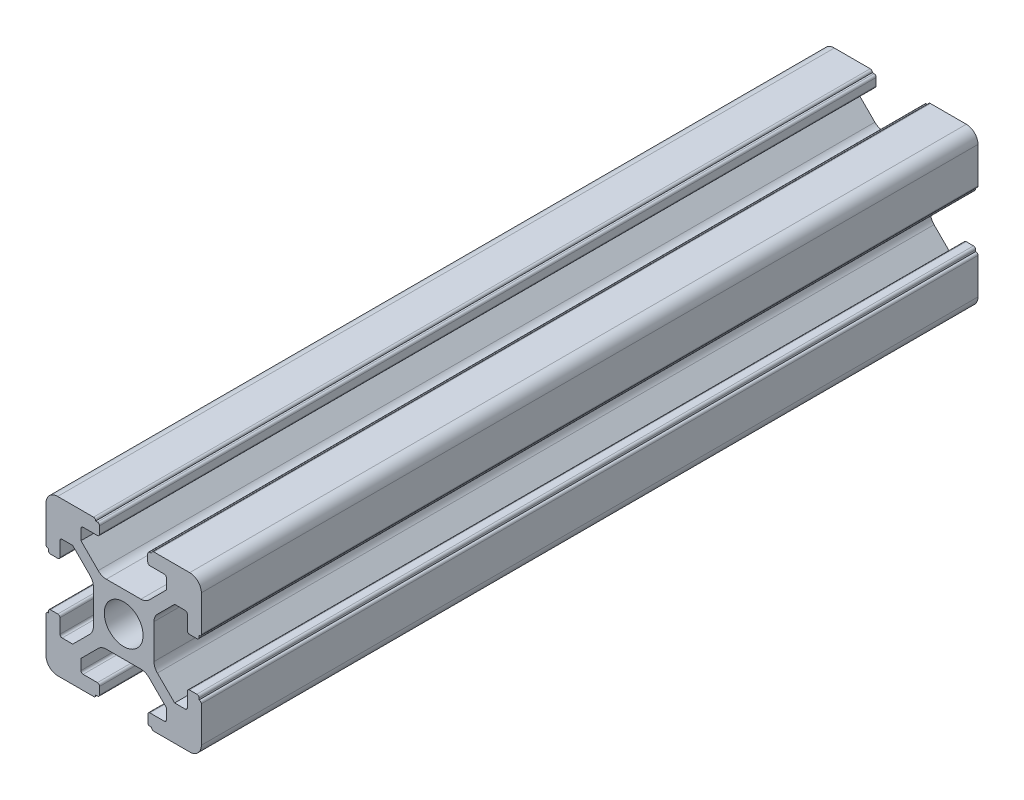
SolidWorks part; units mm, degrees
material "1060 Alloy"
ref_plane "Front Plane" through (0, 0, 0) normal (0, 0, 1) x (1, 0, 0)
ref_plane "Top Plane" through (0, 0, 0) normal (0, 1, 0) x (1, 0, 0)
ref_plane "Right Plane" through (0, 0, 0) normal (1, 0, 0) x (0, 0, -1)
sketch "Sketch1" plane through (0, 0, 0) normal (0, 0, 1) x (1, 0, 0)
  line L0 (3.8995, 3.9005) -> (10.4604, 10.4604) construction
  line L2 (-3.9002, 2.2177) -> (-3.9002, -2.2208)
  line L5 (-3.9005, 3.899) -> (3.9001, -3.8986) construction
  line L6 (-3.9, -3.901) -> (3.8995, 3.9005) construction
  line L7 (-0.0002, 10) -> (-0.0002, -9.9996) construction
  line L8 (-0.0002, -9.9996) -> (-0.0002, 10) construction
  line L9 (5.5006, 6.5619) -> (3.2793, 4.3405)
  line L14 (-10.0002, 9.9996) -> (9.9994, -10) construction
  line L15 (-9.9999, -10.0001) -> (9.9998, 10) construction
  line L16 (6.5613, 5.5012) -> (4.3401, 3.28)
  line L17 (-5.5002, 6.5603) -> (-3.279, 4.3391)
  line L18 (-6.5609, 5.4996) -> (-4.3395, 3.2783)
  line L19 (7.9206, 5.5012) -> (6.5613, 5.5012)
  line L20 (8.2006, 3.3812) -> (8.2006, 5.2212)
  line L21 (9.4206, 3.1012) -> (8.4806, 3.1012)
  line L22 (9.7006, 3.6012) -> (9.7006, 3.3812)
  line L23 (-8.5002, 9.9996) -> (-3.8802, 9.9996)
  line L24 (-3.6002, 9.7196) -> (-3.6002, 9.6996)
  line L25 (-3.6002, 9.6996) -> (-3.3802, 9.6996)
  line L26 (-3.1002, 9.4196) -> (-3.1002, 8.4796)
  line L27 (-3.3802, 8.1996) -> (-5.2202, 8.1996)
  line L28 (-5.5002, 7.9196) -> (-5.5002, 6.5603)
  line L29 (-7.9202, 5.4996) -> (-6.5609, 5.4996)
  line L30 (-8.2002, 3.3796) -> (-8.2002, 5.2196)
  line L31 (-9.4202, 3.0996) -> (-8.4802, 3.0996)
  line L32 (-9.7202, 3.5996) -> (-9.7002, 3.5996)
  line L33 (-9.7002, 3.5996) -> (-9.7002, 3.3796)
  line L34 (-10.0002, 8.4996) -> (-10.0002, 3.8796)
  line L35 (10.0006, 8.5012) -> (10.0006, 3.8812)
  line L36 (8.5006, 10.0012) -> (3.8806, 10.0012)
  line L37 (3.6006, 9.7012) -> (3.3806, 9.7012)
  line L38 (3.1006, 9.4212) -> (3.1006, 8.4812)
  line L39 (3.3806, 8.2012) -> (5.2206, 8.2012)
  line L40 (5.5006, 7.9212) -> (5.5006, 6.5619)
  line L41 (6.5629, -5.4996) -> (4.3415, -3.2783)
  line L42 (5.5022, -6.5603) -> (3.281, -4.3391)
  line L43 (5.5022, -7.9196) -> (5.5022, -6.5603)
  line L44 (3.3822, -8.1996) -> (5.2222, -8.1996)
  line L45 (3.1022, -9.4196) -> (3.1022, -8.4796)
  line L46 (3.6022, -9.6996) -> (3.3822, -9.6996)
  line L47 (8.5022, -9.9996) -> (3.8822, -9.9996)
  line L48 (10.0022, -8.4996) -> (10.0022, -3.8796)
  line L49 (9.7022, -3.5996) -> (9.7022, -3.3796)
  line L50 (9.4222, -3.0996) -> (8.4822, -3.0996)
  line L51 (8.2022, -3.3796) -> (8.2022, -5.2196)
  line L52 (7.9222, -5.4996) -> (6.5629, -5.4996)
  line L53 (-5.4986, -6.5619) -> (-3.2773, -4.3405)
  line L54 (-6.5593, -5.5012) -> (-4.3395, -3.2814)
  line L55 (-7.9186, -5.5012) -> (-6.5593, -5.5012)
  line L56 (-8.1986, -3.3812) -> (-8.1986, -5.2212)
  line L57 (-9.4186, -3.1012) -> (-8.4786, -3.1012)
  line L58 (-9.6986, -3.6012) -> (-9.6986, -3.3812)
  line L59 (-9.9986, -8.5012) -> (-9.9986, -3.8812)
  line L60 (-8.4986, -10.0012) -> (-3.8786, -10.0012)
  line L61 (-3.5986, -9.7012) -> (-3.3786, -9.7012)
  line L62 (-3.0986, -9.4212) -> (-3.0986, -8.4812)
  line L63 (-3.3786, -8.2012) -> (-5.2186, -8.2012)
  line L64 (-5.4986, -7.9212) -> (-5.4986, -6.5619)
  line L65 (-2.233, 3.8998) -> (2.2187, 3.9012)
  line L66 (3.9008, 2.234) -> (3.9022, -2.2177)
  line L67 (2.235, -3.8998) -> (-2.2167, -3.9012)
  line L68 (3.6006, 9.7212) -> (3.6006, 9.6996)
  line L69 (9.7006, 3.6012) -> (9.7206, 3.6012)
  line L70 (-9.6986, -3.6012) -> (-9.7186, -3.6012)
  line L71 (-3.5986, -9.7012) -> (-3.5986, -9.7212)
  line L72 (3.6022, -9.6996) -> (3.6022, -9.7196)
  line L73 (9.7222, -3.5996) -> (9.7022, -3.5996)
  arc A0 (-3.6002, 9.7196) -> (-3.8802, 9.9996) centre (-3.8802, 9.7196) ccw
  arc A1 (-3.3802, 9.6996) -> (-3.1002, 9.4196) centre (-3.3802, 9.4196) cw
  arc A2 (-3.1002, 8.4796) -> (-3.3802, 8.1996) centre (-3.3802, 8.4796) cw
  arc A3 (-10.0002, 8.4996) -> (-8.5002, 9.9996) centre (-8.5002, 8.4996) cw
  arc A4 (-8.2002, 3.3796) -> (-8.4802, 3.0996) centre (-8.4802, 3.3796) cw
  arc A5 (-9.4202, 3.0996) -> (-9.7002, 3.3796) centre (-9.4202, 3.3796) cw
  arc A6 (-9.7202, 3.5996) -> (-10.0002, 3.8796) centre (-9.7202, 3.8796) cw
  arc A7 (-3.279, 4.3391) -> (-2.233, 3.8998) centre (-2.2183, 5.3997) ccw
  arc A8 (-4.3395, 3.2783) -> (-3.9002, 2.2177) centre (-5.4002, 2.2177) cw
  arc A9 (-7.9202, 5.4996) -> (-8.2002, 5.2196) centre (-7.9202, 5.2196) ccw
  arc A10 (-5.2202, 8.1996) -> (-5.5002, 7.9196) centre (-5.2202, 7.9196) ccw
  arc A12 (-4.3395, -3.2814) -> (-3.9002, -2.2208) centre (-5.4002, -2.2208) ccw
  arc A13 (8.2006, 5.2212) -> (7.9206, 5.5012) centre (7.9206, 5.2212) ccw
  arc A14 (8.4806, 3.1012) -> (8.2006, 3.3812) centre (8.4806, 3.3812) cw
  arc A15 (9.7006, 3.3812) -> (9.4206, 3.1012) centre (9.4206, 3.3812) cw
  arc A16 (9.7206, 3.6012) -> (10.0006, 3.8812) centre (9.7206, 3.8812) ccw
  arc A17 (8.5006, 10.0012) -> (10.0006, 8.5012) centre (8.5006, 8.5012) cw
  arc A18 (3.6006, 9.7212) -> (3.8806, 10.0012) centre (3.8806, 9.7212) cw
  arc A19 (3.1006, 9.4212) -> (3.3806, 9.7012) centre (3.3806, 9.4212) cw
  arc A20 (3.3806, 8.2012) -> (3.1006, 8.4812) centre (3.3806, 8.4812) cw
  arc A21 (5.5006, 7.9212) -> (5.2206, 8.2012) centre (5.2206, 7.9212) ccw
  arc A22 (3.2793, 4.3405) -> (2.2187, 3.9012) centre (2.2187, 5.4012) cw
  arc A23 (4.3401, 3.28) -> (3.9008, 2.234) centre (5.4007, 2.2193) ccw
  arc A25 (5.2222, -8.1996) -> (5.5022, -7.9196) centre (5.2222, -7.9196) ccw
  arc A26 (3.1022, -8.4796) -> (3.3822, -8.1996) centre (3.3822, -8.4796) cw
  arc A27 (3.3822, -9.6996) -> (3.1022, -9.4196) centre (3.3822, -9.4196) cw
  arc A28 (3.6022, -9.7196) -> (3.8822, -9.9996) centre (3.8822, -9.7196) ccw
  arc A29 (10.0022, -8.4996) -> (8.5022, -9.9996) centre (8.5022, -8.4996) cw
  arc A30 (9.7222, -3.5996) -> (10.0022, -3.8796) centre (9.7222, -3.8796) cw
  arc A31 (9.4222, -3.0996) -> (9.7022, -3.3796) centre (9.4222, -3.3796) cw
  arc A32 (8.2022, -3.3796) -> (8.4822, -3.0996) centre (8.4822, -3.3796) cw
  arc A33 (7.9222, -5.4996) -> (8.2022, -5.2196) centre (7.9222, -5.2196) ccw
  arc A34 (4.3415, -3.2783) -> (3.9022, -2.2177) centre (5.4022, -2.2177) cw
  arc A35 (3.281, -4.3391) -> (2.235, -3.8998) centre (2.2203, -5.3997) ccw
  circle A36 centre (0.001, -0.001) radius 2.5 construction
  arc A37 (-8.1986, -5.2212) -> (-7.9186, -5.5012) centre (-7.9186, -5.2212) ccw
  arc A38 (-8.4786, -3.1012) -> (-8.1986, -3.3812) centre (-8.4786, -3.3812) cw
  arc A39 (-9.6986, -3.3812) -> (-9.4186, -3.1012) centre (-9.4186, -3.3812) cw
  arc A40 (-9.7186, -3.6012) -> (-9.9986, -3.8812) centre (-9.7186, -3.8812) ccw
  arc A41 (-8.4986, -10.0012) -> (-9.9986, -8.5012) centre (-8.4986, -8.5012) cw
  arc A42 (-3.5986, -9.7212) -> (-3.8786, -10.0012) centre (-3.8786, -9.7212) cw
  arc A43 (-3.0986, -9.4212) -> (-3.3786, -9.7012) centre (-3.3786, -9.4212) cw
  arc A44 (-3.3786, -8.2012) -> (-3.0986, -8.4812) centre (-3.3786, -8.4812) cw
  arc A45 (-5.4986, -7.9212) -> (-5.2186, -8.2012) centre (-5.2186, -7.9212) ccw
  arc A46 (-3.2773, -4.3405) -> (-2.2167, -3.9012) centre (-2.2167, -5.4012) cw
  arc A48 (-4.3381, -3.28) -> (-3.8988, -2.234) centre (-5.3987, -2.2193) ccw [skipped]
  point P0 (0, 0)
  point P9 (-0.0002, 0.0002)
  point P12 (-0.0003, -0.0003)
  point P43 (-3.6002, 9.9996)
  point P46 (-3.1002, 9.6996)
  point P49 (-3.1002, 8.1996)
  point P55 (-8.2002, 3.0996)
  point P58 (-9.7002, 3.0996)
  point P61 (-10.0002, 3.5996)
  point P64 (-2.8395, 3.8996)
  point P67 (-3.9002, 2.839)
  point P70 (-8.2002, 5.4996)
  point P73 (-5.5002, 8.1996)
  point P184 (0.001, 0)
  dimension "D14" = 0.28
  dimension "D15" = 0.28
  dimension "D16" = 0.28
  dimension "D17" = 1.5
  dimension "D18" = 0.28
  dimension "D19" = 1.5
  dimension "D20" = 1.5
  dimension "D21" = 0.28
  dimension "D23" = 5
  dimension "D27" = 1.5
  dimension "D1" = 7.8
  dimension "D2" = 7.8
  dimension "D3" = 3.1
  dimension "D4" = 3.6
  dimension "D5" = 20
  dimension "D6" = 20
  dimension "D7" = 0.75
  dimension "D8" = 1.8
  dimension "D9" = 5.5
  dimension "D10" = 6.4
  dimension "D11" = 6.4
  dimension "D12" = 3.7627
  dimension "D13" = 0.3
  dimension "D24" = 4.62
  dimension "D25" = 3.9005
  dimension "D26" = 7.801
  dimension "D22" = 4
extrude "Boss-Extrude1" add sketch "Sketch1" along normal blind 100 contours L53 A46 L67 A35 L42 L43 A25 L44 A26 L45 A27 L46 L72 A28 L47 A29 L48 A30 L73 L49 A31 L50 A32 L51 A33 L52 L41 A34 L66 A23 L16 L19 A13 L20 A14 L21 A15 L22 L69 A16 L35 A17 L36 A18 L68 L37 A19 L38 A20 region at (0.0009, 0, 0)
sketch3d "3DSketch2"
  circle A0 centre (0, 0, 0) radius 2.5
  point P2 (0, 0, 2.5)
extrude "Cut-Extrude1" cut sketch "3DSketch2" along direction (0, 0, 1) on the side of the normal through all contours A0
